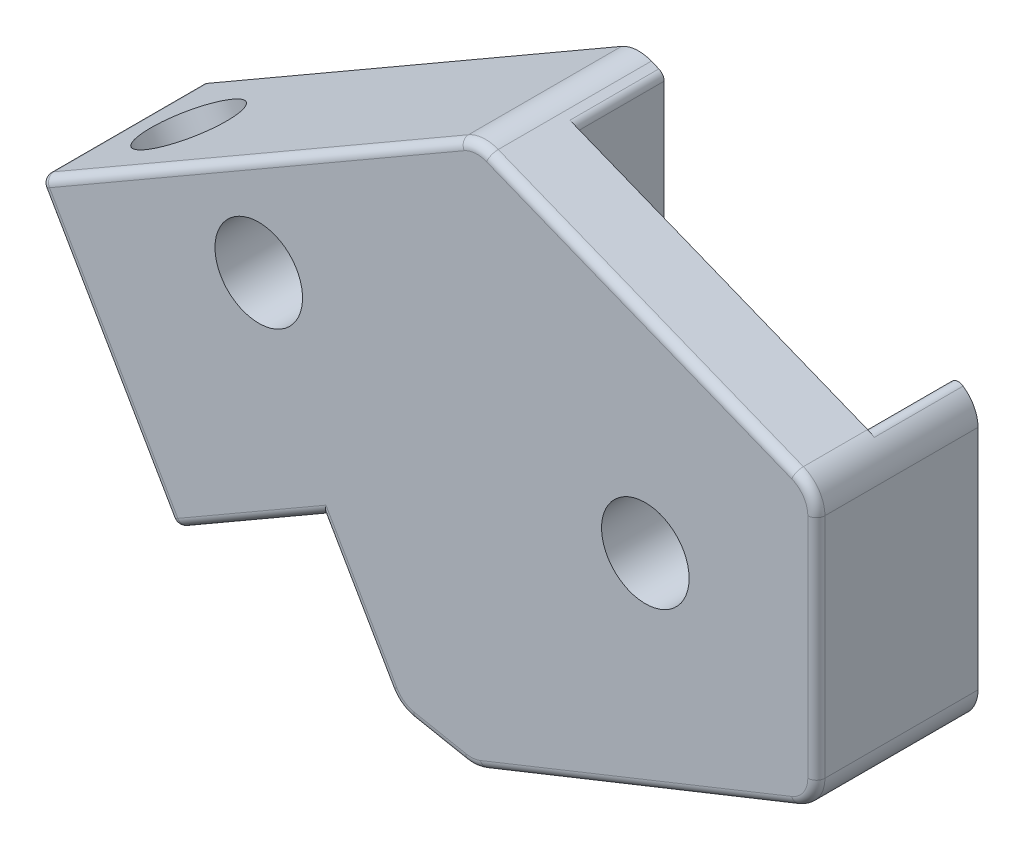
SolidWorks part; units mm, degrees
ref_plane "Front Plane" through (0, 0, 0) normal (0, 0, 1) x (1, 0, 0)
ref_plane "Top Plane" through (0, 0, 0) normal (0, 1, 0) x (1, 0, 0)
ref_plane "Right Plane" through (0, 0, 0) normal (1, 0, 0) x (0, 0, -1)
sketch "Sketch1" plane through (0, 0, 0) normal (0, 0, 1) x (1, 0, 0)
  line L0 (-10.5833, 0) -> (-2.6458, 0) construction
  line L1 (5.2917, -6.35) -> (-10.5833, -12.7)
  line L2 (5.2917, -6.35) -> (5.2917, 6.35)
  line L3 (5.2917, 6.35) -> (-10.5833, 12.7)
  line L4 (-10.5833, -12.7) -> (-10.5833, 12.7)
  line L5 (5.2917, -6.35) -> (-10.5833, 12.7) construction
  line L6 (5.2917, 6.35) -> (-10.5833, -12.7) construction
  line L7 (-2.6458, 0) -> (5.2917, 0) construction
  circle A0 centre (-2.6458, 0) radius 2.032
  point P0 (0, 0)
  dimension "D2" = 4.064
  dimension "D1" = 15.875
  dimension "D3" = 12.7
  dimension "D4" = 25.4
extrude "Boss-Extrude1" add sketch "Sketch1" along normal blind 3.375
sketch "Sketch2" plane through (0, 0, 3.375) normal (0, 0, 1) x (1, 0, 0)
  line L0 (-10.5833, -12.7) -> (5.2917, -6.35) construction
  line L2 (-10.5833, 12.7) -> (-10.5833, -12.7)
  line L4 (-9.2708, 12.175) -> (-9.2708, -12.175)
  line L5 (5.2917, 6.35) -> (-10.5833, 12.7) construction
  line L7 (5.2917, 6.35) -> (5.2917, -6.35)
  line L9 (3.9792, 6.875) -> (3.9792, -6.875)
  line L10 (-10.5833, -12.7) -> (-9.2708, -12.175)
  line L11 (5.2917, 6.35) -> (3.9792, 6.875)
  line L12 (3.9792, -6.875) -> (5.2917, -6.35)
  line L13 (-9.2708, 12.175) -> (-10.5833, 12.7)
  circle A0 centre (-2.6458, 0) radius 6.625 construction
  dimension "D2" = 13.25
extrude "Boss-Extrude2" add sketch "Sketch2" along normal blind 4.125
sketch "Sketch4" plane through (0, 0, 0) normal (0, 0, -1) x (-1, 0, 0)
  line L0 (10.5833, 12.7) -> (30.836, 1.0071)
  line L2 (24.486, -9.9914) -> (10.5833, -12.7)
  line L3 (10.5833, -12.7) -> (10.5833, 12.7)
  line L4 (30.836, 1.0071) -> (24.486, -9.9914)
  circle A0 centre (20.5846, 2.3012) radius 2.032
  circle A1 centre (2.6458, 0) radius 2.032 construction
  dimension "D1" = 17.9387
  dimension "D2" = 2.3012
  dimension "D3" = 30
  dimension "D4" = 9.525
  dimension "D5" = 12.7
extrude "Boss-Extrude3" add sketch "Sketch4" against normal up to surface (7.5 mm away) up to face at (-9.9271, 0, 7.5)
sketch "Sketch5" plane through (-8.1451, 14.1077, 0) normal (-0.5, 0.866, 0) x (0.866, 0.5, 0)
  line L0 (-26.2012, -3.75) -> (-22.4512, -3.75) construction
  line L1 (-26.2012, -7.5) -> (-26.2012, 0) construction
  line L2 (-22.4512, -3.75) -> (-22.4512, 0) construction
  line L3 (-26.2012, 0) -> (-2.8154, 0) construction
  circle A0 centre (-22.4512, -3.75) radius 2.032
  dimension "D1" = 4.064
extrude "Cut-Extrude1" cut sketch "Sketch5" against normal through all
ref_plane "Plane1" through (-1.7951, 3.1092, 0) normal (-0.5, 0.866, 0) x (0.866, 0.5, 0)
sketch "Sketch6" plane through (-1.7951, 3.1092, 0) normal (-0.5, 0.866, 0) x (0.866, 0.5, 0)
  line L0 (-18.2637, -7.5) -> (-18.2637, 0)
  line L1 (-26.2012, -7.5) -> (-2.8154, -7.5) construction
  line L2 (-26.2012, 0) -> (-2.8154, 0) construction
  line L3 (-18.2637, 0) -> (-26.2012, 0)
  line L4 (-26.2012, 0) -> (-26.2012, -7.5)
  line L5 (-26.2012, -7.5) -> (-18.2637, -7.5)
  dimension "D1" = 7.9375
extrude "Cut-Extrude2" cut sketch "Sketch6" against normal through all
fillet "Fillet1" radius 1.5875 5 edges at (5.2917, -6.35, 3.75) (5.2917, 6.35, 3.75) (-10.5833, 12.7, 3.75) (-14.1589, -12.0034, 3.75) (-10.5833, -12.7, 3.75)
fillet "Fillet2" radius 0.3969 19 edges at (3.9792, -6.875, 5.4375) (3.9792, 6.875, 5.4375) (5.0187, 6.1652, 0) (5.2917, 0, 0) (5.0187, -6.1652, 0) (-2.9277, -9.6377, 0) (-2.7869, 9.5814, 0) (-16.0662, -8.6999, 0) (-14.0677, -11.8757, 0) (-12.2458, -12.3761, 0) (-10.5897, -12.6329, 0) (-21.0434, 6.6609, 0) (-10.5707, 12.5232, 0) (-21.0489, -8.007, 0) (-27.661, -4.4921, 0) (-30.836, 1.0071, 3.75) (-24.486, -9.9914, 3.75) (-9.2708, -12.175, 5.4375) (-9.2708, 12.175, 5.4375)
mirror "Mirror1" about plane through (0, 0, 7.5) normal (0, 0, 1) of bodies 106
delete or keep bodies "Body-Delete/Keep 1" type delete bodies bodies 106
